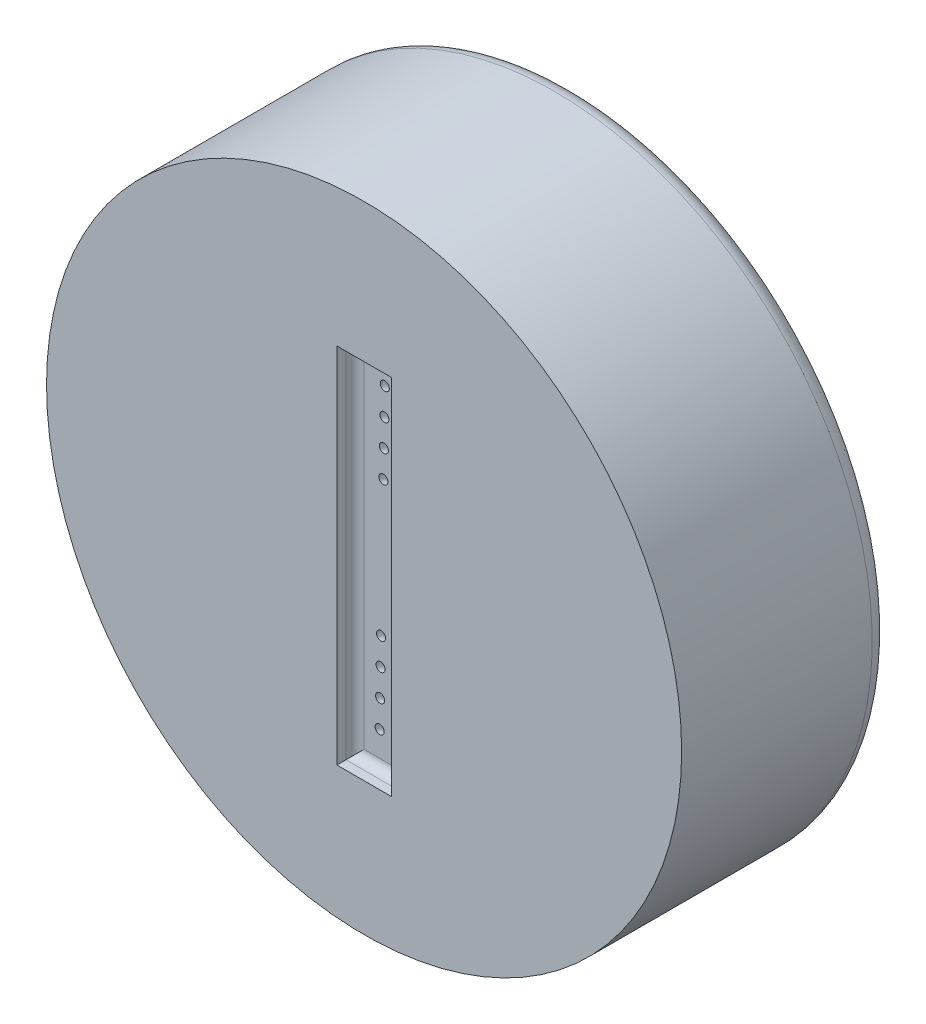
SolidWorks part; units mm, degrees
ref_plane "Front Plane" through (0, 0, 0) normal (0, 0, 1) x (1, 0, 0)
ref_plane "Top Plane" through (0, 0, 0) normal (0, 1, 0) x (1, 0, 0)
ref_plane "Right Plane" through (0, 0, 0) normal (1, 0, 0) x (0, 0, -1)
sketch "Sketch1" plane through (0, 0, 0) normal (0, 0, 1) x (1, 0, 0)
  circle A0 centre (0, 10.3) radius 35
  circle A1 centre (0.282, 26.8276) radius 0.5 construction
  circle A2 centre (0.2308, 23.828) radius 0.5 construction
  circle A3 centre (0.1797, 20.8285) radius 0.5 construction
  circle A12 centre (0.1285, 17.8289) radius 0.5 construction
  circle A13 centre (-0.1285, 2.7711) radius 0.5 construction
  circle A14 centre (-0.1797, -0.2285) radius 0.5 construction
  circle A15 centre (-0.2308, -3.228) radius 0.5 construction
  circle A16 centre (-0.282, -6.2276) radius 0.5 construction
  circle A17 centre (0.282, 26.8276) radius 0.5
  circle A18 centre (0.2308, 23.828) radius 0.5
  circle A19 centre (0.1797, 20.8285) radius 0.5
  circle A20 centre (0.1285, 17.8289) radius 0.5
  circle A21 centre (-0.1285, 2.7711) radius 0.5
  circle A22 centre (-0.1797, -0.2285) radius 0.5
  circle A23 centre (-0.2308, -3.228) radius 0.5
  circle A24 centre (-0.282, -6.2276) radius 0.5
  dimension "D2" = 70
extrude "Boss-Extrude1" add sketch "Sketch1" along normal blind 4
sketch "Sketch2" plane through (0, 0, 4) normal (0, 0, 1) x (1, 0, 0)
  line L1 (-3, 30) -> (3, 30)
  line L2 (-3, 30) -> (-3, -10)
  line L3 (-3, -10) -> (3, -10)
  line L4 (3, 30) -> (3, -10)
  circle A0 centre (0, 10.3) radius 35 construction
  dimension "D1" = 3
  dimension "D2" = 3
  dimension "D3" = 40
  dimension "D4" = 30
extrude "Cut-Extrude1" cut sketch "Sketch2" against normal blind 2
fillet "Fillet1" radius 1 4 edges at (0, -10, 2) (0, 30, 2) (-3, 10, 2) (3, 10, 2)
sketch "Sketch3" plane through (0, 0, 0) normal (0, 0, -1) x (-1, 0, 0)
  circle A0 centre (0, 10.3) radius 30
  circle A1 centre (0, 10.3) radius 35 construction
  dimension "D1" = 5
extrude "Extrude-Thin1" add sketch "Sketch3" along normal blind 19 thin thin type one direction wall 5
fillet "Fillet2" radius 2 9 edges at (-30, 10.3, 0) (0.782, 26.8276, 0) (0.7308, 23.828, 0) (0.6797, 20.8285, 0) (0.6285, 17.8289, 0) (0.3715, 2.7711, 0) (0.3203, -0.2285, 0) (0.2692, -3.228, 0) (0.218, -6.2276, 0)
fillet "Fillet3" radius 2 2 edges at (-30, 10.3, -19) (-35, 10.3, -19)
